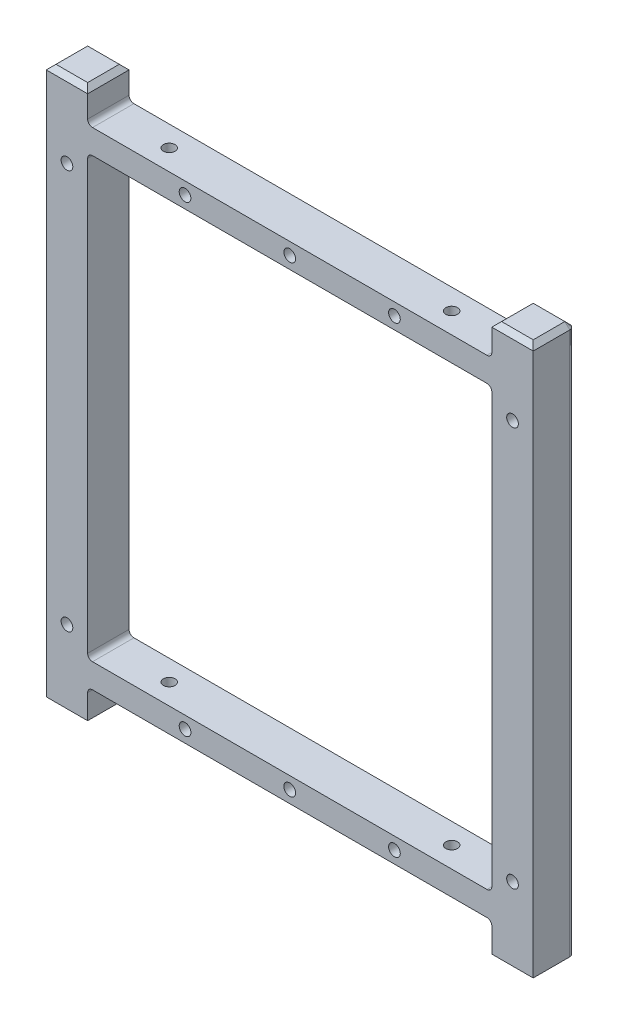
SolidWorks part; units mm, degrees
material "5052-H34"
ref_plane "Frontal" through (0, 0, 0) normal (0, 0, 1) x (1, 0, 0)
ref_plane "Superior" through (0, 0, 0) normal (0, 1, 0) x (1, 0, 0)
ref_plane "Direito" through (0, 0, 0) normal (1, 0, 0) x (0, 0, -1)
sketch "Sketch1" plane through (0, 0, 0) normal (0, 0, 1) x (1, 0, 0)
  line L1 (-50, -56.75) -> (50, -56.75)
  line L2 (-50, -56.75) -> (-50, 56.75)
  line L3 (-50, 56.75) -> (50, 56.75)
  line L4 (50, -56.75) -> (50, 56.75)
  line L5 (-50, -56.75) -> (50, 56.75) construction
  line L6 (-50, 56.75) -> (50, -56.75) construction
  point P0 (0, 0)
  dimension "D1" = 113.5
  dimension "D2" = 100
extrude "Boss-Extrude1" add sketch "Sketch1" along normal mid plane 8.5
sketch "Sketch4" plane through (0, 0, 4.25) normal (0, 0, 1) x (1, 0, 0)
  line L0 (-50, 56.75) -> (-50, -56.75) construction
  line L1 (-40.5, -44.75) -> (40.5, -44.75)
  line L2 (-41.5, -43.75) -> (-41.5, 44.25)
  line L3 (-40.5, 45.25) -> (40.5, 45.25)
  line L4 (41.5, -43.75) -> (41.5, 44.25)
  line L5 (-40.5, -43.75) -> (40.5, 44.25) construction
  line L6 (-40.5, 44.25) -> (40.5, -43.75) construction
  line L7 (50, 56.75) -> (-50, 56.75) construction
  line L8 (-41.5, 56.75) -> (41.5, 56.75)
  line L9 (-41.5, 56.75) -> (-41.5, 51.25)
  line L10 (-40.5, 50.25) -> (40.5, 50.25)
  line L11 (41.5, 56.75) -> (41.5, 51.25)
  line L12 (-50, -56.75) -> (50, -56.75) construction
  line L13 (-41.5, -56.75) -> (41.5, -56.75)
  line L14 (-41.5, -56.75) -> (-41.5, -50.75)
  line L15 (-40.5, -49.75) -> (40.5, -49.75)
  line L16 (41.5, -56.75) -> (41.5, -50.75)
  line L17 (50, -56.75) -> (50, 56.75) construction
  arc A0 (-41.5, 51.25) -> (-40.5, 50.25) centre (-40.5, 51.25) ccw
  arc A1 (40.5, 50.25) -> (41.5, 51.25) centre (40.5, 51.25) ccw
  arc A2 (-40.5, 45.25) -> (-41.5, 44.25) centre (-40.5, 44.25) ccw
  arc A3 (40.5, 45.25) -> (41.5, 44.25) centre (40.5, 44.25) cw
  arc A4 (41.5, -43.75) -> (40.5, -44.75) centre (40.5, -43.75) cw
  arc A5 (-40.5, -44.75) -> (-41.5, -43.75) centre (-40.5, -43.75) cw
  arc A6 (-40.5, -49.75) -> (-41.5, -50.75) centre (-40.5, -50.75) ccw
  arc A7 (40.5, -49.75) -> (41.5, -50.75) centre (40.5, -50.75) cw
  point P0 (1.8681, -1.8902)
  dimension "D11" = 1
  dimension "D12" = 1
  dimension "D13" = 1
  dimension "D14" = 1
  dimension "D15" = 1
  dimension "D16" = 1
  dimension "D17" = 1
  dimension "D18" = 1
  dimension "D1" = 8.5
  dimension "D2" = 8.5
  dimension "D3" = 8.5
  dimension "D4" = 6.5
  dimension "D5" = 8.5
  dimension "D6" = 8.5
  dimension "D7" = 7
  dimension "D8" = 5
  dimension "D9" = 5
  dimension "D10" = 8.5
extrude "Cut-Extrude1" cut sketch "Sketch4" against normal through all
hole_wizard "M2 Hole1-C" positions "Sketch6" profile "Sketch5" hole size "M2" standard "DIN"
sketch "Sketch6" plane through (0, 0, 4.25) normal (0, 0, 1) x (1, 0, 0)
  line L0 (-50, 56.75) -> (-50, -56.75) construction
  line L1 (50, -56.75) -> (50, 56.75) construction
  line L2 (-40.5, 50.25) -> (40.5, 50.25) construction
  line L3 (40.5, -49.75) -> (-40.5, -49.75) construction
  point P0 (-45.75, -40.75)
  point P2 (45.75, -40.75)
  point P4 (-45.75, 41.25)
  point P6 (45.75, 41.25)
  dimension "D1" = 4.25
  dimension "D2" = 4.25
  dimension "D3" = 9
  dimension "D4" = 9
sketch "Sketch5" plane through (-45.75, -40.75, 4.25) normal (1, 0, 0) x (0, -1, 0)
  line L0 (0, 0) -> (0, 3.721)
  line L1 (0, 3.721) -> (1.2, 3)
  line L2 (1.2, 3) -> (1.2, 0)
  line L5 (1.2, 0) -> (0, 0)
  line L10 (0, 3.721) -> (-1.2, 3) construction
  line L11 (0, -6.35) -> (0, 107.95) construction
  dimension "Hole Dia." = 2.4
  dimension "Hole Depth" = 3
  dimension "Drill Angle" = 118
hole_wizard "M2 Hole2-D" positions "Sketch26" profile "Sketch24" hole size "M2" standard "DIN"
sketch "Sketch26" plane through (0, 0, 4.25) normal (0, 0, 1) x (1, 0, 0)
  line L0 (40.5, 45.25) -> (-40.5, 45.25) construction
  line L1 (-50, 56.75) -> (-50, -56.75) construction
  line L2 (50, -56.75) -> (50, 56.75) construction
  line L3 (-40.5, -44.75) -> (40.5, -44.75) construction
  point P0 (-21.5, 47.75)
  point P2 (21.5, 47.75)
  point P4 (-21.5, -47.25)
  point P6 (21.5, -47.25)
  dimension "D1" = 2.5
  dimension "D2" = 28.5
  dimension "D3" = 28.5
  dimension "D4" = 2.5
sketch "Sketch24" plane through (-21.5, 47.75, 4.25) normal (1, 0, 0) x (0, -1, 0)
  line L0 (0, 0) -> (0, 5.721)
  line L1 (0, 5.721) -> (1.2, 5)
  line L2 (1.2, 5) -> (1.2, 0)
  line L5 (1.2, 0) -> (0, 0)
  line L10 (0, 5.721) -> (-1.2, 5) construction
  line L11 (0, -6.35) -> (0, 107.95) construction
  dimension "Hole Dia." = 2.4
  dimension "Hole Depth" = 5
  dimension "Drill Angle" = 118
hole_wizard "M2 Hole3-E" positions "Sketch13" profile "Sketch12" hole size "M2" standard "DIN"
sketch "Sketch13" plane through (0, 0, 4.25) normal (0, 0, 1) x (1, 0, 0)
  line L0 (40.5, -49.75) -> (-40.5, -49.75) construction
  line L1 (-40.5, 50.25) -> (40.5, 50.25) construction
  point P0 (0, 47.75)
  point P2 (0, -47.25)
  dimension "D1" = 2.5
  dimension "D2" = 2.5
sketch "Sketch12" plane through (0, 47.75, 4.25) normal (1, 0, 0) x (0, -1, 0)
  line L0 (0, 0) -> (0, 4.721)
  line L1 (0, 4.721) -> (1.2, 4)
  line L2 (1.2, 4) -> (1.2, 0)
  line L5 (1.2, 0) -> (0, 0)
  line L10 (0, 4.721) -> (-1.2, 4) construction
  line L11 (0, -6.35) -> (0, 107.95) construction
  dimension "Hole Dia." = 2.4
  dimension "Hole Depth" = 4
  dimension "Drill Angle" = 118
hole_wizard "M2 Hole4-F" positions "Sketch23" profile "Sketch22" hole size "M2" standard "DIN"
sketch "Sketch23" plane through (0, 50.25, 0) normal (0, 1, 0) x (1, 0, 0)
  line L0 (-40.5, 4.25) -> (40.5, 4.25) construction
  line L1 (-41.5, 4.25) -> (-41.5, -4.25) construction
  line L2 (41.5, 4.25) -> (41.5, -4.25) construction
  point P0 (-29, 0)
  point P2 (29, 0)
  dimension "D1" = 4.25
  dimension "D2" = 12.5
  dimension "D3" = 12.5
sketch "Sketch22" plane through (-29, 50.25, 0) normal (1, 0, 0) x (0, 0, 1)
  line L0 (0, 0) -> (0, 10.721)
  line L1 (0, 10.721) -> (1.2, 10)
  line L2 (1.2, 10) -> (1.2, 0)
  line L5 (1.2, 0) -> (0, 0)
  line L10 (0, 10.721) -> (-1.2, 10) construction
  line L11 (0, -6.35) -> (0, 107.95) construction
  dimension "Hole Dia." = 2.4
  dimension "Hole Depth" = 10
  dimension "Drill Angle" = 118
hole_wizard "M2 Hole5-G" positions "Sketch17" profile "Sketch16" hole size "M2" standard "DIN"
sketch "Sketch17" plane through (0, -49.75, 0) normal (0, -1, 0) x (-1, 0, 0)
  line L0 (41.5, 4.25) -> (41.5, -4.25) construction
  line L1 (-41.5, 4.25) -> (-41.5, -4.25) construction
  line L2 (-40.5, -4.25) -> (40.5, -4.25) construction
  point P0 (29, 0)
  point P2 (-29, 0)
  dimension "D1" = 12.5
  dimension "D2" = 12.5
  dimension "D3" = 4.25
sketch "Sketch16" plane through (-29, -49.75, 0) normal (1, 0, 0) x (0, 0, -1)
  line L0 (0, 0) -> (0, 10.721)
  line L1 (0, 10.721) -> (1.2, 10)
  line L2 (1.2, 10) -> (1.2, 0)
  line L5 (1.2, 0) -> (0, 0)
  line L10 (0, 10.721) -> (-1.2, 10) construction
  line L11 (0, -6.35) -> (0, 107.95) construction
  dimension "Hole Dia." = 2.4
  dimension "Hole Depth" = 10
  dimension "Drill Angle" = 118
hole_wizard "M2 Hole6-H" positions "Sketch21" profile "Sketch20" hole size "M2" standard "DIN"
sketch "Sketch21" plane through (0, 0, -4.25) normal (0, 0, -1) x (-1, 0, 0)
  line L0 (40.5, 50.25) -> (-40.5, 50.25) construction
  line L1 (-41.5, 51.25) -> (-41.5, 56.75) construction
  line L2 (41.5, 56.75) -> (41.5, 51.25) construction
  line L3 (-40.5, -49.75) -> (40.5, -49.75) construction
  point P0 (-35.5, 47.75)
  point P2 (35.5, 47.75)
  point P4 (-35.5, -47.25)
  point P6 (35.5, -47.25)
  dimension "D1" = 2.5
  dimension "D2" = 6
  dimension "D3" = 6
  dimension "D4" = 2.5
sketch "Sketch20" plane through (35.5, 47.75, -4.25) normal (1, 0, 0) x (0, 1, 0)
  line L0 (0, 0) -> (0, 5.721)
  line L1 (0, 5.721) -> (1.2, 5)
  line L2 (1.2, 5) -> (1.2, 0)
  line L5 (1.2, 0) -> (0, 0)
  line L10 (0, 5.721) -> (-1.2, 5) construction
  line L11 (0, -6.35) -> (0, 107.95) construction
  dimension "Hole Dia." = 2.4
  dimension "Hole Depth" = 5
  dimension "Drill Angle" = 118
fillet "Fillet1" radius 1 2 edges at (-50, 0, -4.25) (50, 0, -4.25)
chamfer "Chamfer1" distance 1 angle 45 20 edges at (-41.5, -56.75, 0) (-45.75, -56.75, 4.25) (-50, -56.75, 0.5) (-49.7071, -56.75, -3.9571) (-45.25, -56.75, -4.25) (-45.75, 56.75, 4.25) (-50, 56.75, 0.5) (-49.7071, 56.75, -3.9571) (-45.25, 56.75, -4.25) (-41.5, 56.75, 0) (45.75, -56.75, 4.25) (41.5, -56.75, 0) (45.25, -56.75, -4.25) (49.7071, -56.75, -3.9571) (50, -56.75, 0.5) (49.7071, 56.75, -3.9571) (50, 56.75, 0.5) (45.75, 56.75, 4.25) (41.5, 56.75, 0) (45.25, 56.75, -4.25)
